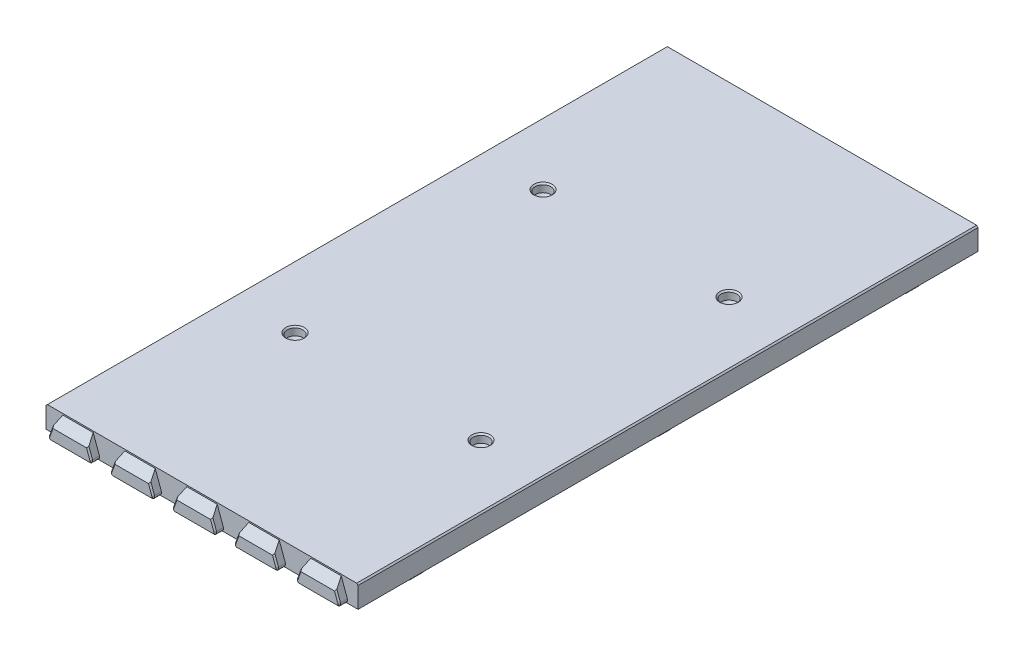
SolidWorks part; units mm, degrees
ref_plane "Front Plane" through (0, 0, 0) normal (0, 0, 1) x (1, 0, 0)
ref_plane "Top Plane" through (0, 0, 0) normal (0, 1, 0) x (1, 0, 0)
ref_plane "Right Plane" through (0, 0, 0) normal (1, 0, 0) x (0, 0, -1)
sketch "Sketch1" plane through (0, 0, 0) normal (0, 0, 1) x (1, 0, 0)
  line L0 (0, 0) -> (0, 8) construction
  line L1 (-56.625, 0) -> (0, 0) construction
  line L2 (-56.625, 0) -> (-56.625, 8)
  line L3 (-56.625, 8) -> (56.625, 8)
  line L5 (-56.625, 0) -> (-54.625, 0)
  line L6 (-54.625, 0) -> (-54.625, 6)
  line L7 (-54.625, 6) -> (54.625, 6)
  line L9 (54.625, 0) -> (54.625, 6)
  line L10 (56.625, 0) -> (54.625, 0)
  line L11 (56.625, 0) -> (56.625, 8)
  point P8 (0, 6)
  dimension "D2" = 6
  dimension "D1" = 56.625
  dimension "D3" = 2
  dimension "D4" = 2
extrude "Boss-Extrude1" add sketch "Sketch1" against normal blind 112.5
sketch "Sketch7" plane through (0, 0, 0) normal (0, 0, 1) x (1, 0, 0)
  line L2 (-54.625, 0) -> (54.625, 0)
  line L13 (-54.625, 0) -> (-54.625, 6)
  line L15 (-54.625, 6) -> (54.625, 6)
  line L16 (54.625, 0) -> (54.625, 6)
  line M3 (-54.625, 0) -> (-54.625, 6)
  line M4 (-54.625, 6) -> (54.625, 6)
  line M5 (54.625, 6) -> (54.625, 0)
extrude "Boss-Extrude7" add sketch "Sketch7" against normal blind 1 contours M4 M3 | M5 region at (0, 3, 0)
sketch "Sketch2" plane through (0, 0, 0) normal (0, 0, 1) x (1, 0, 0)
  line L14 (39.6618, 8) -> (36.75, 0)
  line L15 (56.625, 8) -> (-56.625, 8) construction
  line L16 (-56.625, 0) -> (56.625, 0) construction
  line L17 (36.75, 0) -> (53.25, 0)
  line L18 (39.6618, 8) -> (50.3382, 8)
  line L19 (-56.625, 0) -> (56.625, 0) construction
  line L21 (50.3382, 8) -> (53.25, 0)
  line L24 (33.75, 0) -> (33.75, 8) construction
  line L27 (17.1618, 8) -> (14.25, 0)
  line L28 (17.1618, 8) -> (27.8382, 8)
  line L29 (14.25, 0) -> (30.75, 0)
  line L30 (27.8382, 8) -> (30.75, 0)
  line L31 (-5.3382, 8) -> (-8.25, 0)
  line L32 (-5.3382, 8) -> (5.3382, 8)
  line L33 (-8.25, 0) -> (8.25, 0)
  line L34 (5.3382, 8) -> (8.25, 0)
  line L35 (-27.8382, 8) -> (-30.75, 0)
  line L36 (-27.8382, 8) -> (-17.1618, 8)
  line L37 (-30.75, 0) -> (-14.25, 0)
  line L38 (-17.1618, 8) -> (-14.25, 0)
  line L39 (39.6618, 8) -> (17.1618, 8) construction
  line L40 (56.25, 8) -> (56.25, 0) construction
  line L41 (56.625, 0) -> (56.625, 8) construction
  line L42 (-56.25, 8) -> (-56.25, 0) construction
  line L43 (-56.625, 8) -> (-56.625, 0) construction
  line L44 (-50.3382, 8) -> (-53.25, 0)
  line L45 (-50.3382, 8) -> (-39.6618, 8)
  line L46 (-53.25, 0) -> (-36.75, 0)
  line L47 (-39.6618, 8) -> (-36.75, 0)
  point P22 (45, 8)
  point P23 (22.5, 8)
  dimension "D1" = 70
  dimension "D2" = 0.375
  dimension "D3" = 3
  dimension "D4" = 3
  dimension "D5" = 70
  dimension "D7" = 22.5
  dimension "D8" = 22.5
  dimension "D9" = 0.375
  dimension "D10" = 25.5
  dimension "D11" = 8
  dimension "D6" = 5
extrude "Boss-Extrude4" add sketch "Sketch2" along normal blind 3
sketch "Sketch8" plane through (0, 0, 0) normal (0, -1, 0) x (1, 0, 0)
  line L0 (-56.625, -22.5) -> (56.625, -22.5) construction
  line L2 (56.625, -112.5) -> (56.625, 0) construction
  line L3 (-56.625, 0) -> (-53.25, 0) construction
  line L4 (-55.25, -24.9559) -> (-55.25, -20.0441)
  line L5 (-55.25, -20.0441) -> (-51.25, -21.5)
  line L6 (-51.25, -21.5) -> (-51.25, -23.5)
  line L7 (-55.25, -112.5) -> (-55.25, -110.0441)
  line L8 (-55.25, -110.0441) -> (-51.25, -111.5)
  line L9 (-51.25, -111.5) -> (-51.25, -112.5)
  line L10 (-54.625, -112.5) -> (54.625, -112.5) construction
  line L11 (-51.25, -112.5) -> (-55.25, -112.5)
  line L12 (-55.25, -24.9559) -> (-51.25, -23.5)
  line L13 (0, -112.5) -> (0, 0) construction
  line L23 (-56.625, -112.5) -> (-56.625, 0) construction
  line L24 (55.25, -24.9559) -> (51.25, -23.5)
  line L25 (51.25, -21.5) -> (51.25, -23.5)
  line L26 (55.25, -20.0441) -> (51.25, -21.5)
  line L27 (55.25, -24.9559) -> (55.25, -20.0441)
  line L28 (-56.625, -112.5) -> (-54.625, -112.5) construction
  line L29 (51.25, -112.5) -> (55.25, -112.5)
  line L30 (51.25, -111.5) -> (51.25, -112.5)
  line L31 (55.25, -110.0441) -> (51.25, -111.5)
  line L32 (55.25, -112.5) -> (55.25, -110.0441)
  point P19 (-51.25, -22.5)
  point P32 (51.25, -22.5)
  dimension "D1" = 22.5
  dimension "D3" = 70
  dimension "D4" = 4
  dimension "D5" = 1.375
  dimension "D6" = 4
  dimension "D7" = 70
  dimension "D8" = 1
  dimension "D9" = 1
extrude "Boss-Extrude8" add sketch "Sketch8" against normal up to next and the other way blind 2
chamfer "Chamfer4" distance 0.5 angle 45 14 edges at (-51.25, -2, -112) (-53.25, -2, -110.7721) (-55.25, -2, -111.2721) (-53.25, -2, -24.2279) (-51.25, -2, -22.5) (-53.25, -2, -20.7721) (51.25, -2, -22.5) (53.25, -2, -24.2279) (53.25, -2, -20.7721) (55.25, -2, -22.5) (51.25, -2, -112) (55.25, -2, -111.2721) (53.25, -2, -110.7721) (-55.25, -2, -22.5)
fillet "Fillet4" radius 1 10 edges at (53.25, 0, 1.5) (36.75, 0, 1.5) (30.75, 0, 1.5) (14.25, 0, 1.5) (8.25, 0, 1.5) (-8.25, 0, 1.5) (-14.25, 0, 1.5) (-30.75, 0, 1.5) (-36.75, 0, 1.5) (-53.25, 0, 1.5)
chamfer "Chamfer6" distance 0.5 angle 45 25 edges at (38.4501, 4.671, 3) (51.5499, 4.671, 3) (45, 0, 3) (-29.0499, 4.671, 3) (-22.5, 0, 3) (-15.9501, 4.671, 3) (-6.5499, 4.671, 3) (0, 0, 3) (6.5499, 4.671, 3) (15.9501, 4.671, 3) (29.0499, 4.671, 3) (22.5, 0, 3) (-51.5499, 4.671, 3) (-45, 0, 3) (-38.4501, 4.671, 3) (-52.641, 0.4264, 3) (-37.359, 0.4264, 3) (-30.141, 0.4264, 3) (-14.859, 0.4264, 3) (-7.641, 0.4264, 3) (7.641, 0.4264, 3) (14.859, 0.4264, 3) (30.141, 0.4264, 3) (37.359, 0.4264, 3) (52.641, 0.4264, 3)
fillet "Fillet2" radius 2 23 edges at (0, 6, -1) (-54.625, 3, -110.2716) (-52.9375, 6, -110.8858) (-51.25, 6, -112) (-54.625, 3, -1) (-52.9375, 6, -20.8858) (-54.625, 3, -20.2716) (-54.625, 6, -67.5) (-51.25, 6, -22.5) (-52.9375, 6, -24.1142) (-54.625, 3, -24.7284) (54.625, 6, -10.6358) (54.625, 3, -1) (-54.625, 6, -10.6358) (54.625, 3, -24.7284) (54.625, 3, -20.2716) (54.625, 3, -110.2716) (51.25, 6, -112) (52.9375, 6, -110.8858) (52.9375, 6, -20.8858) (51.25, 6, -22.5) (54.625, 6, -67.5) (52.9375, 6, -24.1142)
mirror "Mirror2" about plane through (0, 0, -112.5) normal (0, 0, 1) of "Fillet4", "Boss-Extrude1", "Boss-Extrude7", "Boss-Extrude4", "Boss-Extrude8", "Chamfer4", "Fillet2", "Chamfer6"
sketch "Sketch9" plane through (0, 0, 0) normal (0, 1, 0) x (1, 0, 0)
  line L16 (0, 112.5) -> (0, 0) construction
  line L17 (-56.625, 112.5) -> (56.625, 112.5) construction
  line L18 (-56.625, 115.4563) -> (-56.625, 109.5437) construction
  line L20 (56.625, 225) -> (56.625, 0) construction
  circle A0 centre (-33.75, 67.5) radius 5
  circle A4 centre (33.75, 67.5) radius 5
  circle A5 centre (33.75, 157.5) radius 5
  circle A6 centre (-33.75, 157.5) radius 5
  point P23 (0, 112.5)
  point P24 (0, 112.5)
  dimension "D3" = 10
  dimension "D1" = 45
  dimension "D2" = 33.75
extrude "Boss-Extrude9" add sketch "Sketch9" along normal up to next
fillet "Fillet3" radius 3 4 edges at (-33.75, 6, -72.5) (-33.75, 6, -162.5) (33.75, 6, -162.5) (33.75, 6, -72.5)
sketch "Sketch10" plane through (0, 0, 0) normal (0, 1, 0) x (1, 0, 0)
  circle A0 centre (-33.75, 157.5) radius 1.85
  circle A1 centre (-33.75, 67.5) radius 1.85
  circle A2 centre (33.75, 67.5) radius 1.85
  circle A3 centre (33.75, 157.5) radius 1.85
  dimension "D1" = 3.7
extrude "Cut-Extrude2" cut sketch "Sketch10" along normal through all
sketch "Sketch11" plane through (0, 8, 0) normal (0, 1, 0) x (1, 0, 0)
  circle A0 centre (-33.75, 157.5) radius 2.85
  circle A1 centre (33.75, 157.5) radius 2.85
  circle A2 centre (33.75, 67.5) radius 2.85
  circle A3 centre (-33.75, 67.5) radius 2.85
  dimension "D1" = 5.7
extrude "Cut-Extrude3" cut sketch "Sketch11" against normal blind 3
chamfer "Chamfer7" distance 1 angle 45 4 edges at (33.75, 5, -155.65) (-33.75, 5, -155.65) (33.75, 5, -65.65) (-33.75, 5, -65.65)
sketch "Sketch12" plane through (0, 0, 0) normal (1, 0, 0) x (0, 0, -1)
  line L0 (0, 7.5) -> (-3, 4.5)
  line L1 (-3, 1.171) -> (-3, 8) construction
  line L2 (-3, 4.5) -> (-3, 7.5)
  line L4 (112.5, 8) -> (112.5, 0) construction
  line L5 (225, 8) -> (0, 8) construction
  line L6 (225, 0) -> (0, 0) construction
  line L10 (0, 1.342) -> (0, 8) construction
  line L11 (-3, 7.5) -> (0, 7.5) construction
  line L12 (0, 7.5) -> (0, 8)
  line L13 (0, 8) -> (-3, 8)
  line L14 (-3, 8) -> (-2.5, 8) construction
  line L15 (-3, 8) -> (-3, 7.5)
  line L16 (228, 7.5) -> (225, 7.5) construction
  line L17 (228, 8) -> (228, 7.5)
  line L18 (225, 8) -> (228, 8)
  line L19 (225, 7.5) -> (225, 8)
  line L20 (228, 4.5) -> (228, 7.5)
  line L21 (225, 7.5) -> (228, 4.5)
  dimension "D1" = 0.5
  dimension "D2" = 3
  dimension "D3" = 45
extrude "Cut-Extrude4" cut sketch "Sketch12" against normal through all both and the other way through all
chamfer "Chamfer8" distance 0.5 angle 45 6 edges at (33.75, 8, -154.65) (-33.75, 8, -154.65) (-33.75, 8, -64.65) (33.75, 8, -64.65) (56.625, 8, -112.5) (-56.625, 8, -112.5)
